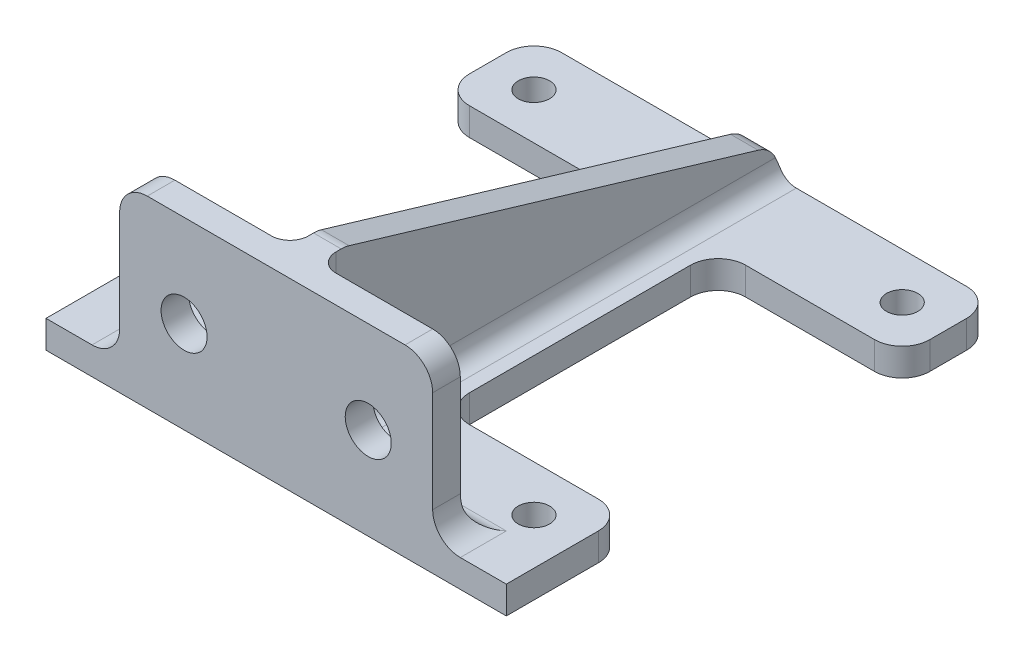
SolidWorks part; units mm, degrees
ref_plane "Plan de face" through (0, 0, 0) normal (0, 0, 1) x (1, 0, 0)
ref_plane "Plan de dessus" through (0, 0, 0) normal (0, 1, 0) x (1, 0, 0)
ref_plane "Plan de droite" through (0, 0, 0) normal (1, 0, 0) x (0, 0, -1)
sketch "Esquisse1" plane through (0, 0, 0) normal (0, 1, 0) x (1, 0, 0)
  line L0 (25, 50) -> (25, 25) construction
  line L1 (0, 0) -> (50, 0)
  line L2 (0, 0) -> (0, 50)
  line L3 (0, 50) -> (50, 50)
  line L4 (50, 0) -> (50, 50)
  line L5 (25, 25) -> (50, 25) construction
  line L6 (45, 45) -> (5, 45) construction
  line L7 (5, 45) -> (5, 5) construction
  circle A0 centre (5, 5) radius 1.7
  circle A1 centre (5, 45) radius 1.7
  circle A2 centre (45, 45) radius 1.7
  circle A3 centre (45, 5) radius 1.7
  dimension "D1" = 3.4
  dimension "D2" = 40
  dimension "D3" = 50
extrude "Boss.-Extru.1" add sketch "Esquisse1" along normal blind 3
sketch "Esquisse2" plane through (0, 0, 0) normal (0, 0, 1) x (1, 0, 0)
  line L0 (0, 10) -> (50, 10) construction
  line L1 (0, 0) -> (50, 0)
  line L2 (0, 0) -> (0, 20)
  line L3 (0, 20) -> (50, 20)
  line L4 (50, 0) -> (50, 20)
  line L5 (25, 10) -> (25, 20) construction
  circle A0 centre (15, 10) radius 2.5
  circle A1 centre (35, 10) radius 2.5
  dimension "D2" = 5
  dimension "D1" = 20
  dimension "D3" = 20
extrude "Boss.-Extru.2" add sketch "Esquisse2" along normal blind 3
ref_plane "Plan1" through (25, 0, 0) normal (1, 0, 0) x (0, 0, -1)
sketch "Esquisse3" plane through (25, 0, 0) normal (1, 0, 0) x (0, 0, -1)
  line L0 (0, 20) -> (3, 20)
  line L1 (3, 20) -> (50, 6)
  line L2 (50, 6) -> (50, 3)
  line L3 (50, 3) -> (0, 3)
  line L4 (0, 3) -> (50, 3) construction
  line L5 (0, 3) -> (0, 20)
  dimension "D1" = 3
  dimension "D2" = 3
extrude "Boss.-Extru.3" add sketch "Esquisse3" along normal blind 1.5 and the other way blind 1.5
sketch "Esquisse5" plane through (0, 0, 0) normal (0, 0, -1) x (-1, 0, 0)
  line L0 (0, 20) -> (0, 3) construction
  line L1 (0, 3) -> (-8, 3)
  line L2 (0, 3) -> (0, 20)
  line L3 (0, 20) -> (-8, 20)
  line L4 (-8, 3) -> (-8, 20)
  line L5 (0, 3) -> (-23.5, 3) construction
  line L6 (-23.5, 20) -> (0, 20) construction
  line L7 (-50, 20) -> (-26.5, 20) construction
  line L8 (-50, 3) -> (-42, 3)
  line L9 (-50, 3) -> (-50, 20)
  line L10 (-50, 20) -> (-42, 20)
  line L11 (-42, 3) -> (-42, 20)
  dimension "D1" = 8
  dimension "D2" = 8
extrude "Enlèv. mat.-Extru.2" cut sketch "Esquisse5" against normal blind 10
fillet "Congé1" radius 3 2 edges at (0, 1.5, -50) (50, 1.5, -50)
fillet "Congé2" radius 3 6 edges at (25, 6, -50) (25, 20, -3) (42, 3, 1.5) (42, 20, 1.5) (8, 3, 1.5) (8, 20, 1.5)
fillet "Congé3" radius 2 8 edges at (35.75, 3, 0) (23.5, 11.5, 0) (23.5, 3.3817, -50) (23.5, 3, -25) (26.5, 11.5, 0) (26.5, 3, -25) (26.5, 3.3817, -50) (14.25, 3, 0)
sketch "Esquisse4" plane through (0, 3, 0) normal (0, 1, 0) x (1, 0, 0)
  line L4 (50, -3) -> (50, 47) construction
  line L5 (50, 10) -> (30, 10)
  line L6 (50, 10) -> (50, 40)
  line L7 (50, 40) -> (30, 40)
  line L8 (30, 10) -> (30, 40)
  line L9 (25, 50) -> (25, -3) construction
  line L10 (23.0718, 50) -> (26.9282, 50) construction
  line L11 (39, -3) -> (11, -3) construction
  line L16 (20, 10) -> (20, 40)
  line L17 (0, 40) -> (20, 40)
  line L18 (0, 10) -> (0, 40)
  line L19 (0, 10) -> (20, 10)
  line L20 (21.5, 50) -> (3, 50) construction
  dimension "D1" = 10
  dimension "D2" = 10
  dimension "D3" = 30
extrude "Enlèv. mat.-Extru.1" cut sketch "Esquisse4" against normal through all
fillet "Congé4" radius 3 8 edges at (50, 1.5, -40) (50, 1.5, -10) (30, 1.5, -10) (30, 1.5, -40) (20, 1.5, -10) (0, 1.5, -10) (0, 1.5, -40) (20, 1.5, -40)
